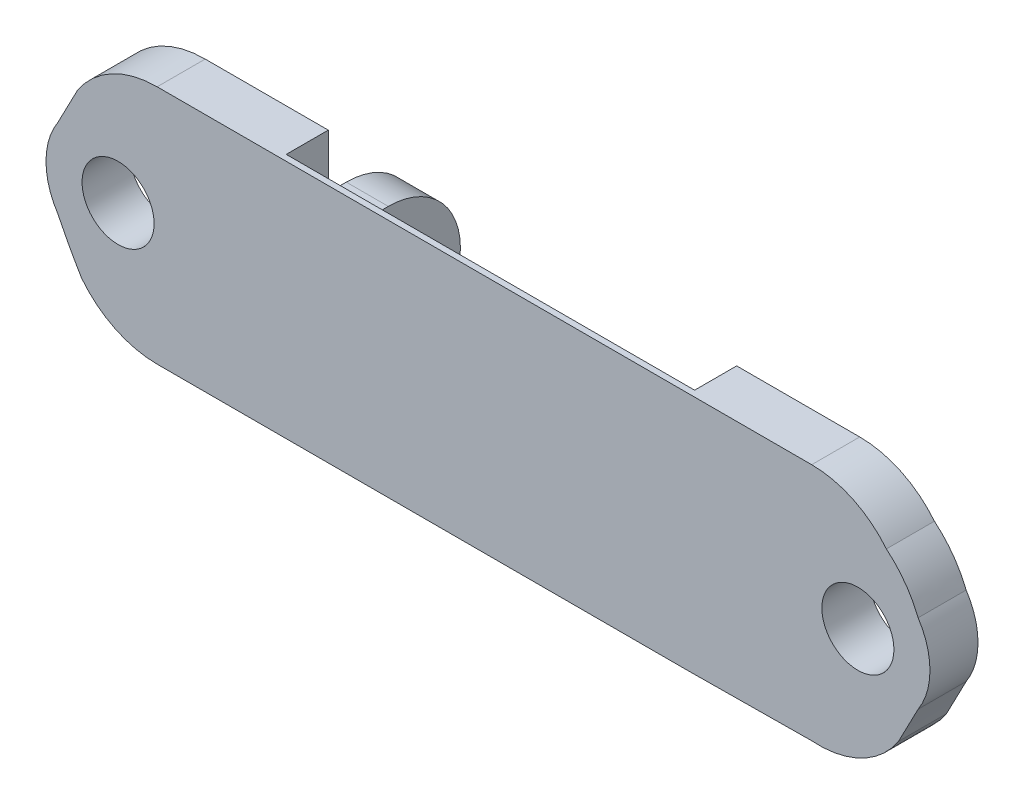
SolidWorks part; units mm, degrees
ref_plane "Front Plane" through (0, 0, 0) normal (0, 0, 1) x (1, 0, 0)
ref_plane "Top Plane" through (0, 0, 0) normal (0, 1, 0) x (1, 0, 0)
ref_plane "Right Plane" through (0, 0, 0) normal (1, 0, 0) x (0, 0, -1)
sketch "Sketch1" plane through (0, 0, 0) normal (0, 0, 1) x (1, 0, 0)
  line L0 (-27.246, 10) -> (-17, 10)
  line L3 (-27.246, -10) -> (-17, -10)
  line L5 (-17, 10) -> (-17, -10)
  line L6 (-17, -10) -> (-16.85, -9.6978)
  arc A0 (-27.246, 10) -> (-33.8759, 6.4363) centre (-27.2666, 2.0893) ccw
  arc A1 (-27.246, -10) -> (-33.5405, -6.9376) centre (-27.246, -2) cw
  arc A2 (-35.515, 3.2939) -> (-35.515, -3.2939) centre (-30.5, 0) ccw
  circle A3 centre (-30.5, 0) radius 3
  spline S0 degree 2 poles (-33.8759, 6.4363) (-34.6716, 4.8526) (-35.515, 3.2939) knots 0 0 0 1 1 1
  spline S1 degree 2 poles (-35.515, -3.2939) (-34.6044, -5.157) (-33.5405, -6.9376) knots 0 0 0 1 1 1
  dimension "D2" = 6.0001
  dimension "D3" = 7.9107
  dimension "D4" = 8
  dimension "D5" = 6
  dimension "D1" = 20
  dimension "D6" = 10.246
  dimension "D7" = 10.246
  dimension "D8" = 17
  dimension "D9" = 27.2666
  dimension "D10" = 30.5
  dimension "D11" = 33.8759
  dimension "D12" = 34.7238
  dimension "D13" = 6.9376
  dimension "D14" = 34.9005
  dimension "D15" = 2.0893
  dimension "D16" = 3.2939
  dimension "D17" = 4.4449
  dimension "D18" = 4.8429
  dimension "D27" = 35.515
  dimension "D28" = 35.515
extrude "Boss-Extrude1" add sketch "Sketch1" along normal blind 4 contours A2 S1 A1 L3 L5 L0 A0 S0 A3 region at (-25.2903, -0.001, 0)
sketch "Sketch5" plane through (-17, 0, 0) normal (1, 0, 0) x (0, 0, -1)
  line L0 (0, 10) -> (0, -10)
  line L1 (5, -10) -> (0, -10)
  line L2 (0, 10) -> (-3.5006, 10)
  line L3 (-3.5006, 10) -> (-2, -2.2928)
  line L4 (-2, -2.2928) -> (-2, -10)
  line L5 (-2, -10) -> (0, -10)
  line L6 (0, -10) -> (5, -10)
  line L7 (5, -10) -> (5, 2) construction
  line L8 (-4, -10) -> (0, -10) construction
  line L9 (-0.5882, 2) -> (5, 2)
  line L10 (-4, 10) -> (0, 10) construction
  line L11 (0, 10) -> (0, -10) construction
  line L12 (11, -4) -> (0, -4) construction
  line L13 (11, -4) -> (8.6, -4)
  line L14 (-3.5006, 10) -> (-4, 10)
  line L15 (-4, 10) -> (-4, -10)
  line L16 (-4, -10) -> (-2, -10)
  arc A0 (5, -10) -> (5, 2) centre (5, -4) ccw
  arc A1 (5.7452, -1.4125) -> (6.5072, -6.55) centre (6, -4) cw
  arc A2 (5.7452, -1.4125) -> (6.5072, -6.55) centre (6, -4) ccw
  line M18 (0, -10) -> (0, 10)
  line M19 (0, 10) -> (-4, 10)
  line M20 (-4, 10) -> (-4, -10)
  line M21 (-4, -10) -> (0, -10)
  dimension "D7" = 6
  dimension "D8" = 2.6
  dimension "D9" = 2.6
  dimension "D1" = 2
  dimension "D2" = 3.5006
  dimension "D3" = 12.3841
  dimension "D4" = 5.5882
  dimension "D5" = 11
  dimension "D6" = 2.4
  dimension "D10" = 5.7452
  dimension "D11" = 6
extrude "Boss-Extrude4" add sketch "Sketch5" against normal blind 3.5 contours L1 A0 L9 A2 A1 M18 region at (-17, 1.8372, -2.5)
extrude "Boss-Extrude6" add sketch "Sketch5<4>" along normal blind 34 contours L4 L3 M19 M20 M21 region at (-17, -1.7689, 3.1498)
sketch "Sketch5<4>" plane through (-17, 0, 0) normal (1, 0, 0) x (0, 0, -1) same geometry as "Sketch5"
sketch "Sketch7" plane through (17, 0, 0) normal (1, 0, 0) x (0, 0, -1)
  line L0 (0, 9.9858) -> (0, -10.0142)
  line L1 (5, -10.0142) -> (0, -10.0142)
  line L2 (0, 9.9858) -> (-3.5006, 9.9858)
  line L3 (-3.5006, 9.9858) -> (-2, -2.307)
  line L4 (-2, -2.307) -> (-2, -10.0142)
  line L5 (-2, -10.0142) -> (0, -10.0142)
  line L6 (0, -10.0142) -> (5, -10.0142)
  line L7 (5, -10.0142) -> (5, 1.9858) construction
  line L8 (-4, 10) -> (-4, -10) construction
  line L9 (-0.5882, 1.9858) -> (5, 1.9858)
  line L10 (-2, -2.2928) -> (-2, -10) construction
  line L12 (11, -4.0142) -> (0, -4.0142) construction
  line L13 (11, -4.0142) -> (8.6, -4.0142)
  line L14 (-3.5006, 9.9858) -> (-4, 9.9858)
  line L15 (-4, 9.9858) -> (-4, -10.0142)
  line L16 (-4, -10.0142) -> (-2, -10.0142)
  line L17 (-3.5006, 10) -> (-4, 10) construction
  arc A0 (5, -10.0142) -> (5, 1.9858) centre (5, -4.0142) ccw
  arc A1 (5.7452, -1.4267) -> (6.5072, -6.5642) centre (6, -4.0142) cw
  arc A2 (5.7452, -1.4267) -> (6.5072, -6.5642) centre (6, -4.0142) ccw
  dimension "D7" = 6
  dimension "D8" = 2.6
  dimension "D9" = 2.6
  dimension "D12" = 0.0142
  dimension "D1" = 2
  dimension "D2" = 3.5006
  dimension "D3" = 12.3841
  dimension "D4" = 5.5882
  dimension "D5" = 11
  dimension "D6" = 2.4
  dimension "D10" = 7.7452
  dimension "D11" = 8
  dimension "D13" = 0.0142
  dimension "D14" = 11.4267
extrude "Boss-Extrude7" add sketch "Sketch7" along normal blind 3.5 separate body contours A2 A1 A0 L9 L0 L1 region at (17, 1.823, -2.5)
sketch "Sketch8" plane through (0, 0, 4) normal (0, 0, 1) x (1, 0, 0)
  line L0 (27.246, -9.9049) -> (17, -10)
  line L1 (17, 10) -> (17, -10) construction
  line L2 (-27.246, 10) -> (17, 10) construction
  line L3 (27.246, 10) -> (17, 10)
  line L5 (17, -10) -> (17, 10)
  line L6 (17, 10) -> (17, -8.6221)
  line L7 (-27.246, -10) -> (17, -10) construction
  arc A0 (27.246, -9.9049) -> (34.4678, -6.3412) centre (27.8437, -2.0168) ccw
  arc A1 (27.246, 10) -> (33.4647, 7.0326) centre (27.246, 2) cw
  arc A2 (36.1069, -3.1988) -> (36.1069, 3.389) centre (31.092, 0.0951) ccw
  circle A3 centre (31.092, 0.0951) radius 3
  spline S0 degree 2 poles (34.4678, -6.3412) (35.2635, -4.7575) (36.1069, -3.1988) knots 0 0 0 1 1 1
  spline S1 degree 2 poles (36.1069, 3.389) (35.2559, 5.531) (33.4647, 7.0326) knots 0 0 0 1 1 1
  line M21 (17, -10) -> (17, 10)
  dimension "D2" = 6.0001
  dimension "D3" = 7.9107
  dimension "D4" = 8
  dimension "D5" = 6
  dimension "D1" = 20
  dimension "D6" = 52.515
  dimension "D7" = 10.246
  dimension "D8" = 10.246
  dimension "D9" = 10.8437
  dimension "D10" = 14.092
  dimension "D11" = 16.4647
  dimension "D12" = 17.4678
  dimension "D13" = 18.3157
  dimension "D14" = 18.4924
  dimension "D16" = 0.0951
  dimension "D17" = 1.3779
  dimension "D18" = 5.6502
  dimension "D19" = 6.8012
  dimension "D20" = 14.938
  dimension "D26" = 19.1069
  dimension "D27" = 19.1069
extrude "Boss-Extrude8" add sketch "Sketch8" against normal up to surface (4 mm away) contours A2 S1 A1 L3 L5 L0 A0 S0 A3 M21 region at (25.5188, -0.0257, 4) up to face at (18.75, -4.0142, 0)
